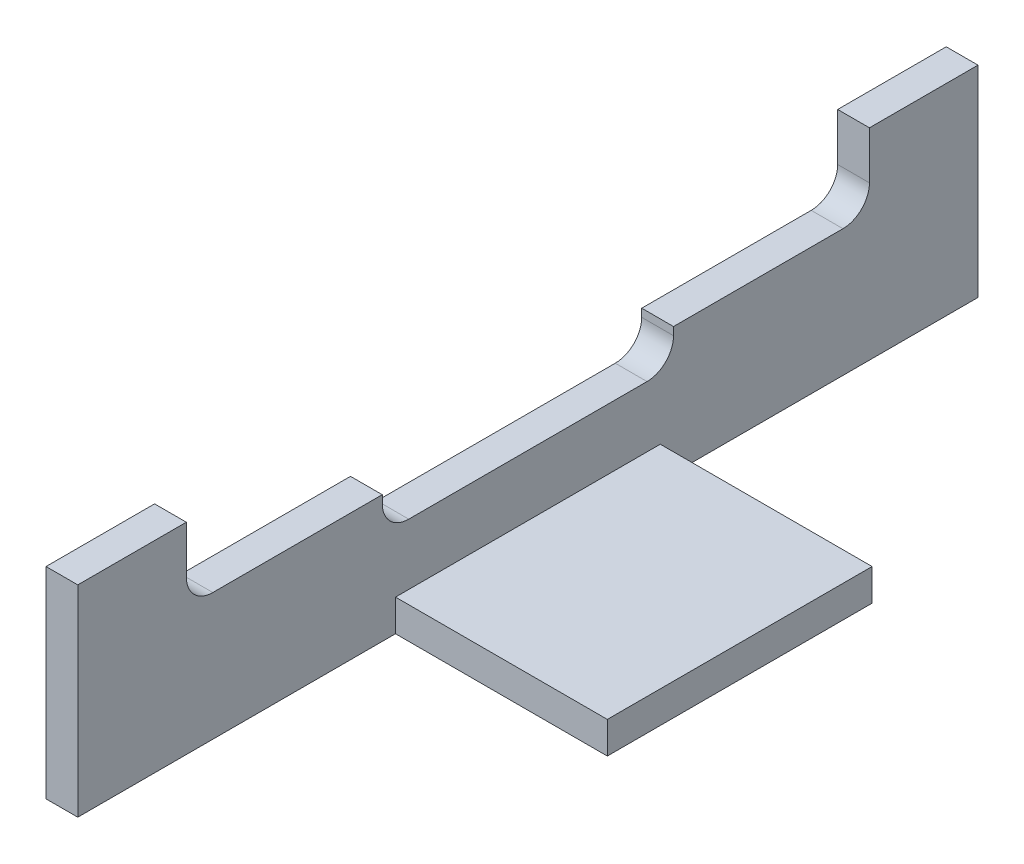
SolidWorks part; units mm, degrees
ref_plane "Alzado" through (0, 0, 0) normal (0, 0, 1) x (1, 0, 0)
ref_plane "Planta" through (0, 0, 0) normal (0, 1, 0) x (1, 0, 0)
ref_plane "Vista lateral" through (0, 0, 0) normal (1, 0, 0) x (0, 0, -1)
sketch "Croquis1" plane through (0, 0, 0) normal (0, 0, 1) x (1, 0, 0)
  line L0 (0, 0) -> (0, 50)
  line L1 (0, 0) -> (50, 0)
  line L2 (6, 6) -> (50, 6)
  line L3 (6, 6) -> (6, 50)
  line L4 (0, 50) -> (6, 50)
  line L5 (50, 6) -> (50, 0)
  dimension "D2" = 50
  dimension "D1" = 6
extrude "Saliente-Extruir1" add sketch "Croquis1" along normal blind 170
sketch "Croquis2" plane through (0, 0, 0) normal (-1, 0, 0) x (0, 0, 1)
  line L0 (170, 35) -> (0, 35) construction
  line L1 (170, 50) -> (170, 0) construction
  line L2 (0, 50) -> (0, 0) construction
  line L3 (170, 6) -> (0, 6) construction
  line L4 (170, 6) -> (0, 6) construction
  line L5 (85, 6) -> (85, 50) construction
  line L6 (170, 50) -> (0, 50) construction
  line L7 (112.5, 17.5) -> (112.5, 50)
  line L8 (112.5, 82.5) -> (57.5, 82.5) construction
  line L9 (112.5, 82.5) -> (112.5, 17.5) construction
  line L10 (112.5, 17.5) -> (57.5, 17.5)
  line L11 (57.5, 82.5) -> (57.5, 17.5) construction
  line L12 (112.5, 82.5) -> (57.5, 17.5) construction
  line L13 (112.5, 17.5) -> (57.5, 82.5) construction
  line L14 (57.5, 17.5) -> (57.5, 50)
  line L15 (57.5, 50) -> (112.5, 50)
  line L16 (149.5, 35) -> (149.5, 50)
  line L17 (130.5, 35) -> (130.5, 50)
  line L18 (130.5, 50) -> (149.5, 50)
  line L19 (39.5, 35) -> (39.5, 50)
  line L20 (20.5, 35) -> (20.5, 50)
  line L21 (39.5, 50) -> (20.5, 50)
  line L22 (170, 0) -> (0, 0) construction
  circle A0 centre (140, 35) radius 9.5 construction
  circle A1 centre (30, 35) radius 9.5 construction
  arc A2 (149.5, 35) -> (130.5, 35) centre (140, 35) cw
  arc A3 (39.5, 35) -> (20.5, 35) centre (30, 35) cw
  dimension "D2" = 19
  dimension "D1" = 35
  dimension "D3" = 55
  dimension "D4" = 55
  dimension "D5" = 17.5
  dimension "D6" = 55
  dimension "D7" = 20.5
  dimension "D8" = 20.5
extrude "Cortar-Extruir1" cut sketch "Croquis2" against normal up to surface (6 mm away) up to face at (6, 28, 85)
sketch "Croquis3" plane through (0, 0, 0) normal (0, -1, 0) x (1, 0, 0)
  line L0 (0, 85) -> (50, 85) construction
  line L1 (0, 170) -> (0, 0) construction
  line L2 (50, 170) -> (50, 0) construction
  line L3 (6, 170) -> (6, 0) construction
  line L4 (50, 0) -> (6, 0)
  line L5 (50, 0) -> (50, 60)
  line L6 (50, 60) -> (6, 60)
  line L7 (6, 0) -> (6, 60)
  line L8 (6, 170) -> (6, 0) construction
  line L9 (50, 110) -> (6, 110)
  line L10 (6, 170) -> (6, 110)
  line L11 (50, 170) -> (6, 170)
  line L12 (50, 170) -> (50, 110)
  line M5 (0, 0) -> (50, 0)
  line M6 (50, 0) -> (50, 170)
  line M7 (50, 170) -> (0, 170)
  dimension "D1" = 60
extrude "Cortar-Extruir2" cut sketch "Croquis3" against normal up to surface (6 mm away) contours L10 L9 M7 M6 | L7 L6 M5 M6 region at (28, 0, 140) region at (28, 0, 30) up to face at (28, 6, 85)
sketch "Croquis4" plane through (0, 0, 0) normal (0, -1, 0) x (1, 0, 0)
  line L0 (46, 60) -> (46, 110)
  line L1 (50, 60) -> (6, 60) construction
  line L2 (50, 110) -> (6, 110) construction
  line L3 (46, 110) -> (50, 110)
  line L4 (50, 110) -> (50, 60)
  line L5 (50, 60) -> (46, 60)
  dimension "D1" = 4
extrude "Cortar-Extruir3" cut sketch "Croquis4" against normal blind 10
sketch "Croquis5" plane through (0, 0, 0) normal (-1, 0, 0) x (0, 0, 1)
  line L0 (170, 38) -> (0, 38) construction
  line L1 (170, 50) -> (170, 0) construction
  line L2 (0, 50) -> (0, 0) construction
  line L3 (170, 50) -> (149.5, 50) construction
  line L4 (170, 38) -> (149.5, 38)
  line L5 (149.5, 38) -> (149.5, 50)
  line L6 (149.5, 50) -> (170, 50)
  line L7 (170, 50) -> (170, 38)
  line L8 (149.5, 35) -> (149.5, 50) construction
  line L9 (112.5, 50) -> (112.5, 38)
  line L10 (112.5, 17.5) -> (112.5, 50) construction
  line L11 (112.5, 38) -> (130.5, 38)
  line L12 (130.5, 50) -> (130.5, 35) construction
  line L13 (130.5, 38) -> (130.5, 50)
  line L14 (130.5, 50) -> (112.5, 50)
  line L15 (85, 17.5) -> (85, 38) construction
  line L16 (57.5, 17.5) -> (112.5, 17.5) construction
  line L17 (39.5, 38) -> (39.5, 50)
  line L18 (57.5, 38) -> (39.5, 38)
  line L19 (57.5, 50) -> (57.5, 38)
  line L20 (39.5, 50) -> (57.5, 50)
  line L21 (20.5, 50) -> (0, 50)
  line L22 (20.5, 38) -> (20.5, 50)
  line L23 (0, 38) -> (20.5, 38)
  line L24 (0, 50) -> (0, 38)
  dimension "D1" = 12
extrude "Cortar-Extruir4" cut sketch "Croquis5" against normal up to surface (6 mm away) up to face at (6, 28.4, 85)
sketch "Croquis6" plane through (0, 0, 0) normal (-1, 0, 0) x (0, 0, 1)
  line L0 (149.5, 38) -> (149.5, 24)
  line L1 (149.5, 24) -> (20.5, 24)
  line L2 (20.5, 24) -> (20.5, 38)
  line L3 (170, 0) -> (0, 0) construction
  line L4 (149.5, 38) -> (20.5, 38)
  dimension "D1" = 24
extrude "Cortar-Extruir5" cut sketch "Croquis6" against normal up to surface (6 mm away) up to face at (6, 23.6, 85)
fillet "Redondeo1" radius 5 2 edges at (3, 24, 149.5) (3, 24, 20.5)
fillet "Redondeo2" radius 5 2 edges at (3, 17.5, 57.5) (3, 17.5, 112.5)
